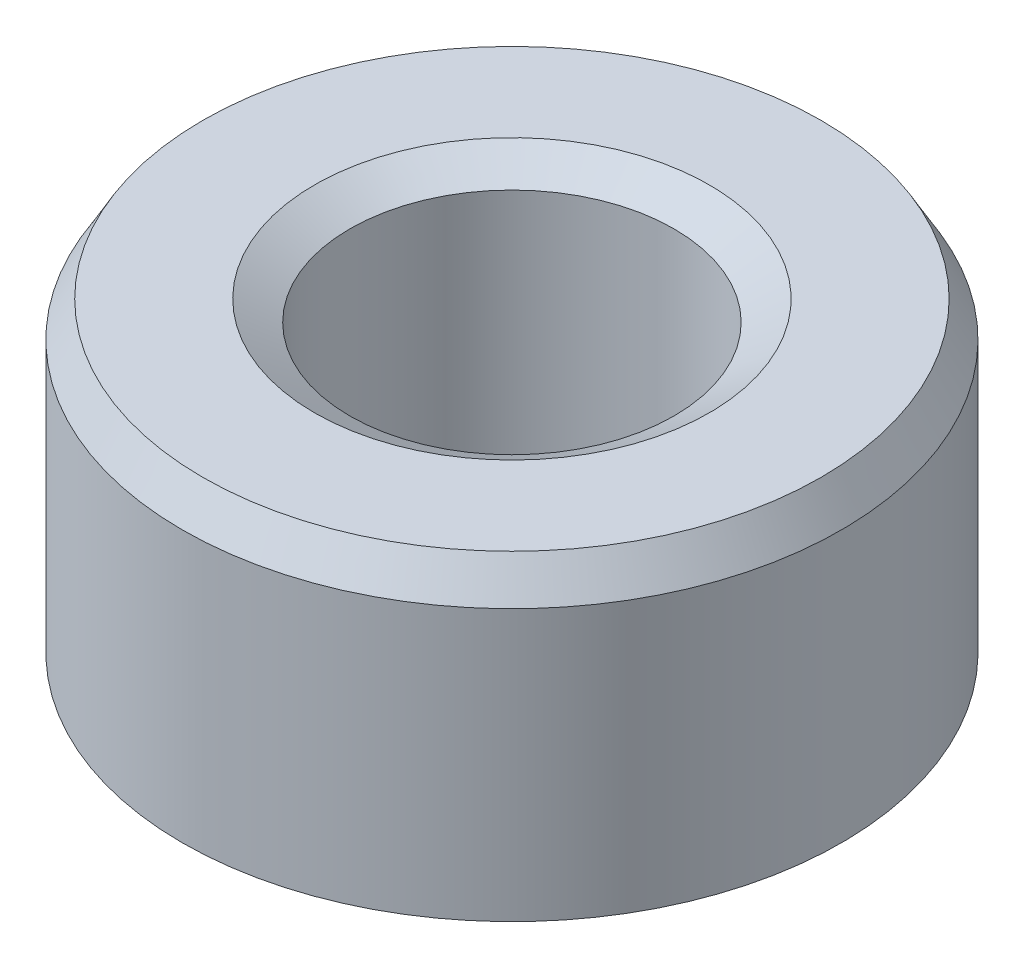
SolidWorks part; units mm, degrees
ref_plane "Front Plane" through (0, 0, 0) normal (0, 0, 1) x (1, 0, 0)
ref_plane "Top Plane" through (0, 0, 0) normal (0, 1, 0) x (1, 0, 0)
ref_plane "Right Plane" through (0, 0, 0) normal (1, 0, 0) x (0, 0, -1)
sketch "Sketch1" plane through (0, 0, 0) normal (0, 1, 0) x (1, 0, 0)
  circle A0 centre (0, 0) radius 35
  dimension "SLEEVE_OD" = 70
extrude "Boss-Extrude1" add sketch "Sketch1" along normal blind 34.6985
sketch "Sketch2" plane through (0, 0, 0) normal (0, 1, 0) x (1, 0, 0)
  circle A0 centre (0, 0) radius 17.2164
  dimension "BORE_D" = 34.4327
extrude "Cut-Extrude1" cut sketch "Sketch2" along normal through all
chamfer "Chamfer1" distance 3.7513 angle 30 4 edges at (0, 34.6985, 17.2164) (0, 0, 17.2164) (0, 0, 35) (0, 34.6985, 35) first distance on face at (0, 34.6985, 17.2164) first distance on face at (0, 0, 17.2164) first distance on face at (0, 34.6985, 35)
